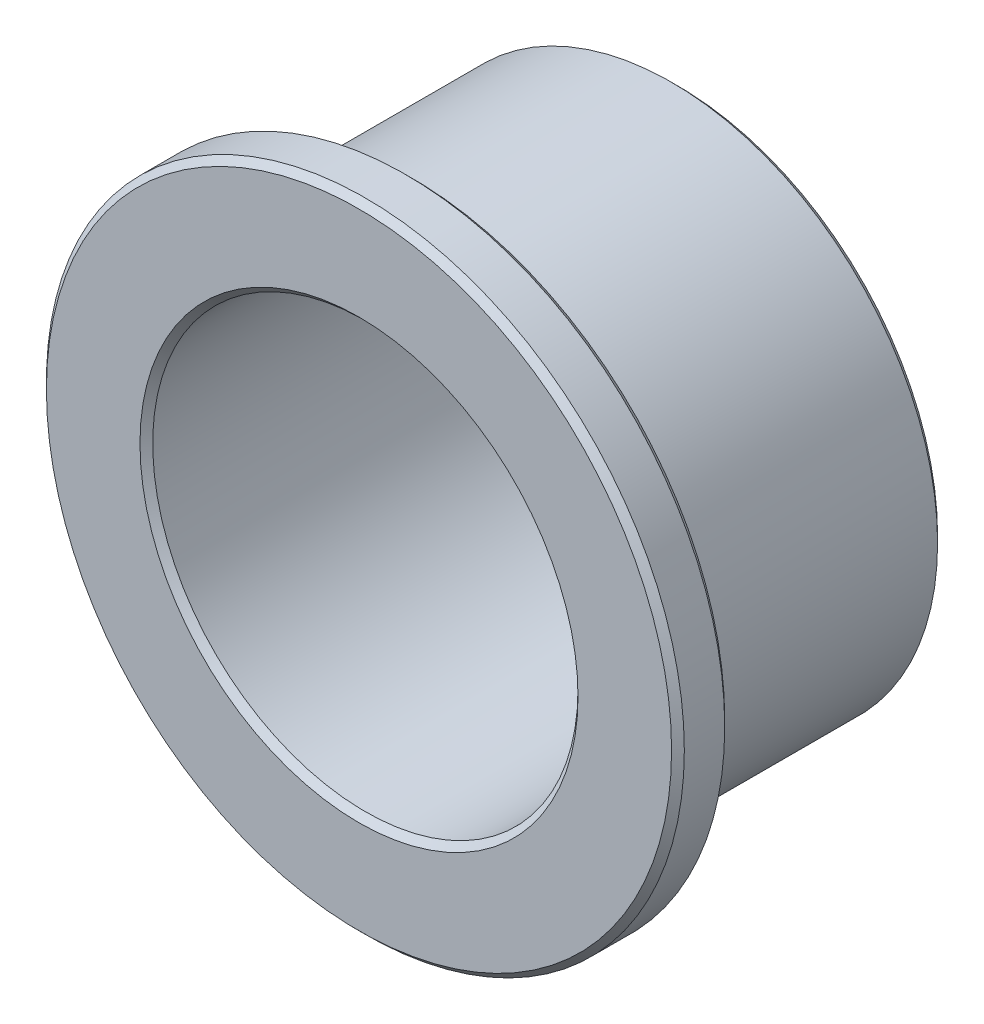
SolidWorks part; units mm, degrees
ref_plane "Front" through (0, 0, 0) normal (0, 0, 1) x (1, 0, 0)
ref_plane "Top" through (0, 0, 0) normal (0, 1, 0) x (1, 0, 0)
ref_plane "Right" through (0, 0, 0) normal (1, 0, 0) x (0, 0, -1)
sketch "Sketch1" plane through (0, 0, 0) normal (0, 0, 1) x (1, 0, 0)
  circle A0 centre (0, 0) radius 12.7
  circle A1 centre (0, 0) radius 15.8877
  circle A2 centre (0, 0) radius 19.05
  dimension "ID" = 25.4
  dimension "OD" = 31.7754
  dimension "Flange OD" = 38.1
sketch "Sketch2" plane through (0, 0, 0) normal (1, 0, 0) x (0, 0, -1)
  line L0 (-9.525, -19.05) -> (9.525, -19.05) construction
  line L1 (0, 19.05) -> (0, -19.05) construction
  line L3 (-6.35, 15.8877) -> (9.525, 15.8877) construction
  point P3 (0, -19.05)
  point P7 (0, 15.8877)
  point P9 (-6.35, -19.05)
  point P10 (-9.525, 19.05)
  point P23 (0, 19.05)
  dimension "Flange Thickness" = 3.175
  dimension "Length" = 19.05
sketch "Sketch3" plane through (0, 0, 0) normal (0, 0, 1) x (1, 0, 0)
  circle A0 centre (0, 0) radius 19.05 construction
  circle A1 centre (0, 0) radius 19.05
  circle A2 centre (0, 0) radius 12.7 construction
  circle A3 centre (0, 0) radius 12.7
extrude "Boss-Extrude1" add sketch "Sketch3" against normal up to vertex (-6.35 mm away) from vertex up to point (0, -19.05, 6.35) starting at point (0, -19.05, 9.525)
sketch "Sketch4" plane through (0, 0, 0) normal (0, 0, 1) x (1, 0, 0)
  circle A0 centre (0, 0) radius 12.7 construction
  circle A1 centre (0, 0) radius 15.8877 construction
  circle A2 centre (0, 0) radius 12.7
  circle A3 centre (0, 0) radius 15.8877
extrude "Boss-Extrude2" add sketch "Sketch4" against normal up to vertex (9.525 mm away) from vertex up to point (0, 15.8877, -9.525) starting at point (0, -19.05, 6.35)
chamfer "Chamfer1" distance 0.381 angle 45 6 edges at (12.7, 0, 9.525) (19.05, 0, 9.525) (19.05, 0, 6.35) (15.8877, 0, 6.35) (12.7, 0, -9.525) (15.8877, 0, -9.525)
equation "\"D1@Chamfer1\"=\"ID@Sketch1\"*0.015"
